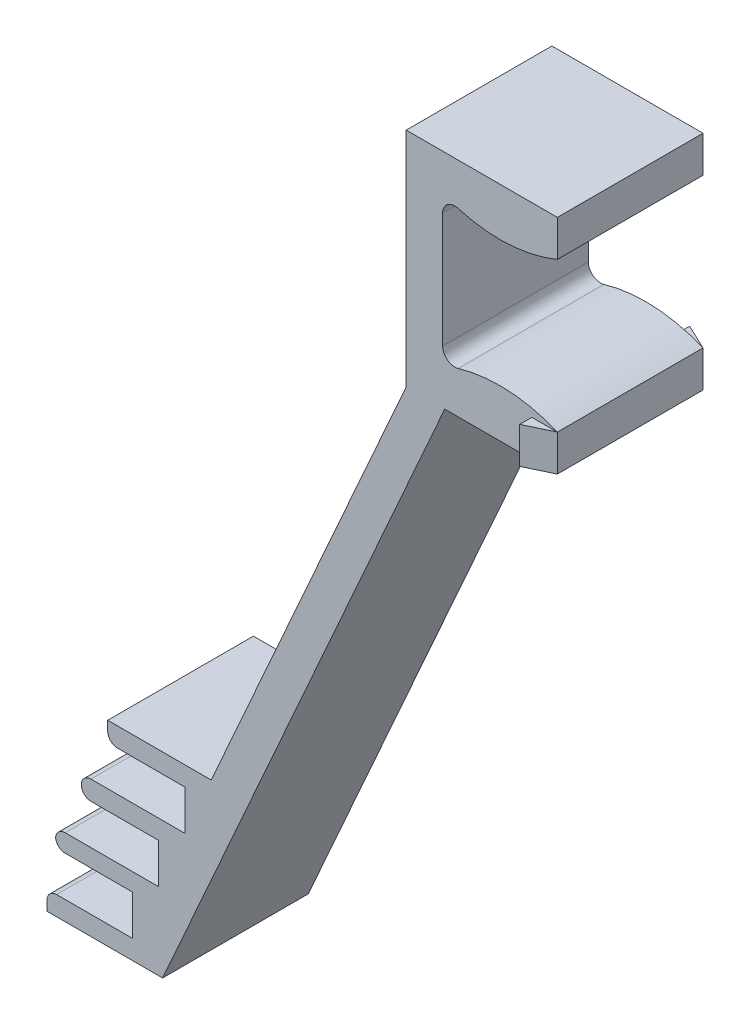
SolidWorks part; units mm, degrees
ref_plane "Front Plane" through (0, 0, 0) normal (0, 0, 1) x (1, 0, 0)
ref_plane "Top Plane" through (0, 0, 0) normal (0, 1, 0) x (1, 0, 0)
ref_plane "Right Plane" through (0, 0, 0) normal (1, 0, 0) x (0, 0, -1)
sketch "Sketch1" plane through (0, 0, 0) normal (0, 0, 1) x (1, 0, 0)
  line L2 (-159.7982, 9.1594) -> (-172.2482, 9.1594)
  line L3 (-172.2482, 9.1594) -> (-172.2482, -9.1594)
  line L7 (-169.2482, -22.8519) -> (-169.2482, 6.1594) construction
  line L12 (-169.2482, 5.1594) -> (-169.2482, 1.9844) construction
  line L13 (-142.8048, 5.1594) -> (-142.8048, -5.1594) construction
  line L15 (-156.5482, 5.1594) -> (21.2518, 5.1594) construction
  line L16 (-156.5482, -5.1594) -> (21.2518, -5.1594) construction
  line L23 (-159.7982, 6.1594) -> (-159.7982, 9.1594)
  line L28 (-164.5232, 5.2094) -> (-144.5007, 5.2094) construction
  line L29 (-156.5482, 5.1594) -> (-169.2482, 5.1594) construction
  line L30 (-169.2482, 6.1594) -> (-169.2482, 5.1594)
  line L34 (-169.2482, 5.1594) -> (-169.2482, -5.1594)
  line L35 (-172.2482, 0) -> (-169.2482, 0) construction
  line L36 (-169.2482, -6.1594) -> (-169.2482, -5.1594)
  line L37 (-159.7982, -6.1594) -> (-159.7982, -9.1594)
  line L38 (-159.7982, -9.1594) -> (-172.2482, -9.1594)
  line L39 (-159.7982, 5.1594) -> (-159.7982, 1.9844) construction
  arc A5 (-169.2482, 6.1594) -> (-159.7982, 6.1594) centre (-164.5232, 17.4347) ccw
  arc A6 (-169.2482, -6.1594) -> (-159.7982, -6.1594) centre (-164.5232, -17.4347) cw
  point P30 (-142.8048, 0)
  dimension "D4" = 3
  dimension "D3" = 3
  dimension "D1" = 0.05
  dimension "D2" = 1
extrude "MainBody" add sketch "Sketch1" along normal mid plane 12
sketch "Sketch3" plane through (0, -9.1594, 0) normal (0, -1, 0) x (1, 0, 0)
  line L0 (-159.7982, -6) -> (-161.8982, -7)
  line L1 (-161.8982, -7) -> (-161.8982, -6)
  line L2 (-172.2482, -6) -> (-159.7982, -6) construction
  line L3 (-161.8982, -6) -> (-159.7982, -6)
  line L4 (-162.8982, -12.7) -> (-162.8982, -6.35) construction
  line L5 (6.8475, 0) -> (-6.8475, 0) construction
  line L6 (-161.8982, 6) -> (-159.7982, 6)
  line L7 (-161.8982, 7) -> (-161.8982, 6)
  line L8 (-159.7982, 6) -> (-161.8982, 7)
  dimension "D1" = 1
  dimension "D2" = 1
extrude "Hook" add sketch "Sketch3" against normal up to vertex (3 mm away) up to point (-159.7982, -6.1594, -6)
fillet "Fillet2" radius 1 2 edges at (-169.2482, 6.1594, 0) (-169.2482, -6.1594, 0)
sketch "Sketch5" [suppressed] plane through (-172.2482, 0, 0) normal (-1, 0, 0) x (0, 0, 1)
  line L1 (-6, 9.1594) -> (6, 9.1594)
  line L2 (-6, 9.1594) -> (-6, -9.1594)
  line L3 (-6, -9.1594) -> (6, -9.1594)
  line L4 (6, 9.1594) -> (6, -9.1594)
extrude "Boss-Extrude1" [suppressed] add sketch "Sketch5" along normal blind 15
sketch "Sketch6" [suppressed] plane through (0, 9.1594, 0) normal (0, 1, 0) x (1, 0, 0)
  line L0 (-187.2482, -6) -> (-187.2482, 6) construction
  circle A0 centre (-182.2482, 0) radius 3.302
  dimension "D1" = 6.604
  dimension "D2" = 5
extrude "Cut-Extrude2" [suppressed] cut sketch "Sketch6" against normal through all
sketch "Sketch7" plane through (-172.2482, 0, 0) normal (-1, 0, 0) x (0, 0, 1)
  circle A0 centre (0, 0) radius 38.1
  dimension "D1" = 76.2
extrude "Boss-Extrude2" [suppressed] add sketch "Sketch7" along normal blind 5
fillet "Fillet3" [suppressed] radius 1
sketch "Sketch8" plane through (0, 0, 6) normal (0, 0, 1) x (1, 0, 0)
  line L6 (-172.2482, -0.635) -> (-173.4343, -0.635)
  line L8 (-172.2482, 0.635) -> (-173.4343, 0.635)
  line L10 (-172.2482, 0.635) -> (-173.4343, 0.635)
  line L11 (-172.2482, 0.635) -> (-172.2482, -0.635)
  line L12 (-161.8982, -9.1594) -> (-161.8982, -6.1594)
  line L13 (-161.8982, -6.1594) -> (-159.7982, -6.1594)
  line L14 (-169.2482, -4.7448) -> (-169.2482, 4.7448)
  line L15 (-159.7982, 6.1594) -> (-159.7982, 9.1594)
  line L16 (-159.7982, 9.1594) -> (-172.2482, 9.1594)
  line L17 (-172.2482, 9.1594) -> (-172.2482, -9.1594)
  line L18 (-172.2482, -9.1594) -> (-161.8982, -9.1594)
  line L19 (-161.8982, -9.1594) -> (-161.8982, -6.1594)
  line L20 (-161.8982, -6.1594) -> (-159.7982, -6.1594)
  line L21 (-169.2482, -4.7448) -> (-169.2482, 4.7448)
  line L22 (-159.7982, 6.1594) -> (-159.7982, 9.1594)
  line L23 (-159.7982, 9.1594) -> (-172.2482, 9.1594)
  line L24 (-172.2482, 9.1594) -> (-172.2482, -9.1594)
  line L25 (-172.2482, -9.1594) -> (-161.8982, -9.1594)
  line L26 (-172.2482, -0.635) -> (-173.4343, -0.635)
  arc A0 (-173.4343, 0.635) -> (-173.4343, -0.635) centre (-174.5342, 0) ccw
  arc A4 (-159.7982, -6.1594) -> (-167.9665, -5.7043) centre (-164.5232, -17.4347) ccw
  arc A5 (-169.2482, -4.7448) -> (-167.9665, -5.7043) centre (-168.2482, -4.7448) ccw
  arc A6 (-167.9665, 5.7043) -> (-169.2482, 4.7448) centre (-168.2482, 4.7448) ccw
  arc A7 (-167.9665, 5.7043) -> (-159.7982, 6.1594) centre (-164.5232, 17.4347) ccw
  arc A8 (-159.7982, -6.1594) -> (-167.9665, -5.7043) centre (-164.5232, -17.4347) ccw
  arc A9 (-169.2482, -4.7448) -> (-167.9665, -5.7043) centre (-168.2482, -4.7448) ccw
  arc A10 (-167.9665, 5.7043) -> (-169.2482, 4.7448) centre (-168.2482, 4.7448) ccw
  arc A11 (-167.9665, 5.7043) -> (-159.7982, 6.1594) centre (-164.5232, 17.4347) ccw
  point P6 (-172.2482, 0)
  line M14 (-172.2482, 9.1594) -> (-172.2482, -9.1594)
  dimension "D2" = 1.27
  dimension "D1" = 0
  dimension "D3" = 2.286
extrude "Slot" [suppressed] add sketch "Sketch8" against normal up to surface (12 mm away) contours L8 A0 L6 M14 up to face at (-165.6835, -0.5599, -6)
sketch "Sketch10" plane through (0, 0, -6) normal (0, 0, -1) x (-1, 0, 0)
  line L0 (167.0732, -9.1594) -> (172.2482, -9.1594)
  line L3 (172.2482, -9.1594) -> (167.0732, -9.1594)
  line L5 (172.2482, -9.1594) -> (187.9767, -44.4861)
  line L6 (195.4932, -61.3685) -> (192.3182, -61.3685)
  line L7 (159.7982, -6.1594) -> (161.8982, -6.1594)
  line L8 (161.8982, -6.1594) -> (161.8982, -9.1594)
  line L9 (161.8982, -9.1594) -> (172.2482, -9.1594)
  line L10 (172.2482, -9.1594) -> (172.2482, 9.1594)
  line L11 (172.2482, 9.1594) -> (159.7982, 9.1594)
  line L12 (159.7982, 9.1594) -> (159.7982, 6.1594)
  line L13 (169.2482, 4.7448) -> (169.2482, -4.7448)
  line L14 (159.7982, -6.1594) -> (161.8982, -6.1594)
  line L15 (161.8982, -6.1594) -> (161.8982, -9.1594)
  line L16 (161.8982, -9.1594) -> (172.2482, -9.1594)
  line L17 (172.2482, -9.1594) -> (172.2482, 9.1594)
  line L18 (172.2482, 9.1594) -> (159.7982, 9.1594)
  line L19 (159.7982, 9.1594) -> (159.7982, 6.1594)
  line L20 (169.2482, 4.7448) -> (169.2482, -4.7448)
  line L21 (195.4932, -61.3685) -> (201.8432, -61.3685)
  line L22 (201.8432, -61.3685) -> (201.8432, -59.781)
  line L23 (201.1364, -55.0185) -> (194.7864, -55.0185)
  line L25 (169.0732, -9.1594) -> (192.3182, -61.3685)
  line L26 (201.1364, -56.479) -> (194.7864, -56.479)
  line L28 (201.8432, -59.781) -> (194.7864, -59.781)
  line L29 (194.7864, -56.479) -> (194.7864, -59.781)
  line L30 (199.016, -51.7165) -> (199.016, -50.129)
  line L32 (199.016, -51.7165) -> (194.7864, -51.7165)
  line L33 (194.7864, -59.781) -> (194.7864, -56.479)
  line L34 (199.016, -51.7165) -> (194.7864, -51.7165)
  line L36 (199.016, -50.129) -> (194.7864, -50.129)
  line L38 (188.4099, -45.2395) -> (196.839, -45.2395)
  line L40 (194.7864, -46.827) -> (196.839, -46.827)
  line L42 (196.839, -46.827) -> (196.839, -45.2395)
  line L43 (187.9767, -44.4861) -> (195.4932, -61.3685)
  line L44 (188.4099, -45.2395) -> (188.3121, -45.2395)
  line L45 (194.7864, -55.0185) -> (192.666, -55.0185)
  line L46 (192.666, -55.0185) -> (192.666, -51.7165)
  line L47 (194.7864, -50.129) -> (190.489, -50.129)
  line L48 (194.7864, -46.827) -> (190.489, -46.827)
  line L49 (192.666, -51.7165) -> (194.7864, -51.7165)
  line L50 (190.489, -50.129) -> (190.489, -46.827)
  line L51 (201.1364, -56.479) -> (201.1364, -55.0185)
  arc A4 (167.9665, -5.7043) -> (159.7982, -6.1594) centre (164.5232, -17.4347) ccw
  arc A5 (159.7982, 6.1594) -> (167.9665, 5.7043) centre (164.5232, 17.4347) ccw
  arc A6 (169.2482, 4.7448) -> (167.9665, 5.7043) centre (168.2482, 4.7448) ccw
  arc A7 (167.9665, -5.7043) -> (169.2482, -4.7448) centre (168.2482, -4.7448) ccw
  arc A8 (167.9665, -5.7043) -> (159.7982, -6.1594) centre (164.5232, -17.4347) ccw
  arc A9 (159.7982, 6.1594) -> (167.9665, 5.7043) centre (164.5232, 17.4347) ccw
  arc A10 (169.2482, 4.7448) -> (167.9665, 5.7043) centre (168.2482, 4.7448) ccw
  arc A11 (167.9665, -5.7043) -> (169.2482, -4.7448) centre (168.2482, -4.7448) ccw
  line M18 (161.8982, -9.1594) -> (172.2482, -9.1594)
  dimension "D5" = 6.35
  dimension "D6" = 3.302
  dimension "D7" = 3.175
  dimension "D8" = 3.175
  dimension "D2" = 57.15
  dimension "D10" = 1.5875
  dimension "D11" = 3.302
  dimension "D3" = 3.302
  dimension "D13" = 114
  dimension "D14" = 114
  dimension "D15" = 6.35
  dimension "D16" = 6.35
  dimension "D17" = 6.35
extrude "Boss-Extrude3" add sketch "Sketch10" against normal up to surface (12 mm away) contours L6 L5 M18 | L28 L43 L21 L22 | L26 L51 L23 L45 L43 L29 | L46 L49 L32 L30 L36 L47 L43 | L43 L50 L48 L40 L42 L38 L44 region at (-182.2832, -35.2639, -6) region at (-198.4884, -60.5608, -6) region at (-192.3162, -46.3221, -6) region at (-196.593, -56.0509, -6) region at (-194.4932, -51.2116, -6) up to face at (-165.6835, -0.5599, 6)
fillet "Fillet4" radius 0.7937 6 edges at (-201.8432, -59.781, 0) (-196.839, -46.827, 0) (-199.016, -50.129, 0) (-199.016, -51.7165, 0) (-201.1364, -55.0185, 0) (-201.1364, -56.479, 0)
equation "\"HookThickness\"= 3mm"
equation "\"D3@Sketch1\"=\"HookThickness\""
equation "\"D4@Sketch1\"=\"HookThickness\""
equation "\"CylinderDiameter\"=3"
equation "\"D1@Sketch7\"=\"CylinderDiameter\""
equation "\"Mount Tolerance\" = .005in"
equation "\"D6@Sketch10\"= .125 + \"Mount Tolerance\""
equation "\"Mount Thickness\"= .0625in"
equation "\"D10@Sketch10\"=\"Mount Thickness\""
equation "\"D11@Sketch10\"= .125 + \"Mount Tolerance\""
equation "\"D3@Sketch10\"= .125 + \"Mount Tolerance\""
equation "\"Mount Angle\"= 114"
equation "\"D14@Sketch10\"=\"Mount Angle\""
equation "\"D13@Sketch10\"= \"Mount Angle\""
